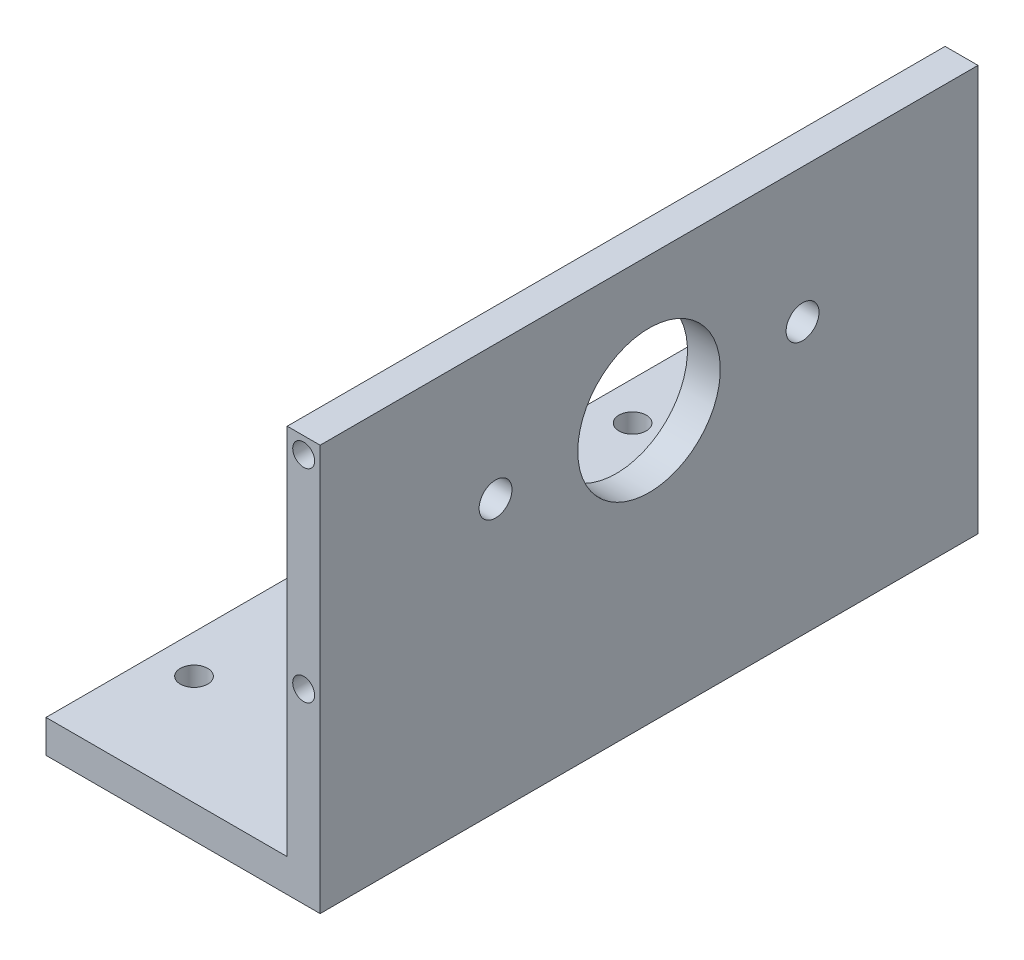
SolidWorks part; units mm, degrees
material "6061 合金"
ref_plane "前视基准面" through (0, 0, 0) normal (0, 0, 1) x (1, 0, 0)
ref_plane "上视基准面" through (0, 0, 0) normal (0, 1, 0) x (1, 0, 0)
ref_plane "右视基准面" through (0, 0, 0) normal (1, 0, 0) x (0, 0, -1)
sketch "草图1" plane through (0, 0, 0) normal (0, 1, 0) x (1, 0, 0)
  line L1 (-25, -60) -> (25, -60)
  line L2 (-25, -60) -> (-25, 60)
  line L3 (-25, 60) -> (25, 60)
  line L4 (25, -60) -> (25, 60)
  line L5 (-25, -60) -> (25, 60) construction
  line L6 (-25, 60) -> (25, -60) construction
  line L7 (25, 60) -> (19, 60)
  line L8 (25, 60) -> (25, -60)
  line L9 (25, -60) -> (19, -60)
  line L10 (19, 60) -> (19, -60)
  point P0 (0, 0)
  dimension "D1" = 50
  dimension "D2" = 120
  dimension "D3" = 6
extrude "凸台-拉伸1" add sketch "草图1" along normal blind 6 contours L10 L3 L2 L1 region at (-3, 0, 0)
extrude "凸台-拉伸2" add sketch "草图1<3>" along normal blind 74 contours L3 L10 L1 L4 region at (22, 0, 0)
sketch "草图1<3>" plane through (0, 0, 0) normal (0, 1, 0) x (1, 0, 0) same geometry as "草图1"
sketch "草图2" plane through (19, 0, 0) normal (-1, 0, 0) x (0, 0, 1)
  line L0 (0, 6) -> (0, 74) construction
  line L1 (-60, 6) -> (60, 6) construction
  line L2 (-60, 74) -> (60, 74) construction
  line L3 (0, 49.5) -> (-60, 49.5) construction
  line L4 (0, 49.5) -> (28, 49.5) construction
  line L5 (-60, 74) -> (-60, 6) construction
  circle A0 centre (0, 49.5) radius 13
  circle A1 centre (-28, 49.5) radius 3
  circle A2 centre (28, 49.5) radius 3
  dimension "D1" = 26
  dimension "D2" = 43.5
  dimension "D3" = 6
  dimension "D4" = 28
  dimension "D5" = 60
extrude "切除-拉伸1" cut sketch "草图2" against normal through all
sketch "草图3" plane through (0, 6, 0) normal (0, 1, 0) x (1, 0, 0)
  line L0 (-25, -60) -> (-25, 60) construction
  line L1 (12, -40) -> (-18, -40) construction
  line L2 (12, -40) -> (12, 40) construction
  line L3 (12, 40) -> (-18, 40) construction
  line L4 (-18, -40) -> (-18, 40) construction
  line L5 (12, -40) -> (-18, 40) construction
  line L6 (12, 40) -> (-18, -40) construction
  circle A0 centre (-18, 40) radius 2.5
  circle A1 centre (12, 40) radius 2.5
  circle A2 centre (-18, -40) radius 2.5
  circle A3 centre (12, -40) radius 2.5
  point P0 (0, 0)
  dimension "D3" = 7
  dimension "D1" = 30
  dimension "D2" = 80
extrude "切除-拉伸2" cut sketch "草图3" against normal blind 10
sketch "草图4" plane through (0, 0, -60) normal (0, 0, -1) x (-1, 0, 0)
  line L0 (-19, 74) -> (-25, 74) construction
  circle A0 centre (-22, 34) radius 2
  circle A1 centre (-22, 71) radius 2
  dimension "D1" = 37
  dimension "D2" = 3
extrude "切除-拉伸3" cut sketch "草图4" against normal blind 20
ref_plane "基准面1" through (0, 0, 0) normal (0, 0, -1) x (-1, 0, 0)
mirror "镜向1" about plane through (0, 0, 0) normal (0, 0, -1) of "切除-拉伸3"
